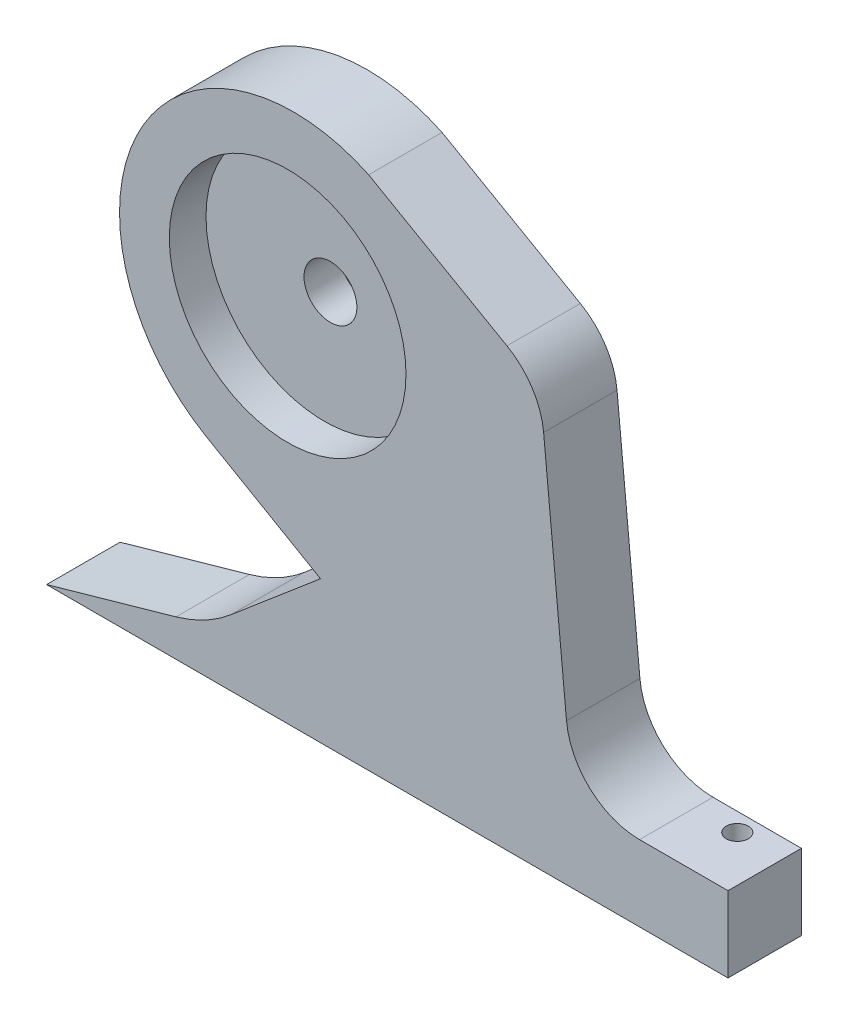
SolidWorks part; units mm, degrees
ref_plane "Front Plane" through (0, 0, 0) normal (0, 0, 1) x (1, 0, 0)
ref_plane "Top Plane" through (0, 0, 0) normal (0, 1, 0) x (1, 0, 0)
ref_plane "Right Plane" through (0, 0, 0) normal (1, 0, 0) x (0, 0, -1)
sketch "Sketch1" plane through (0, 0, 0) normal (0, 0, 1) x (1, 0, 0)
  line L0 (21.2946, 15.4992) -> (22.7802, 0.0334)
  line L2 (-2.5397, 33.9855) -> (16.2995, 23.2268)
  line L3 (22.7802, 0.0334) -> (24.4112, -16.9452)
  line L4 (34.3653, -25.989) -> (46.4112, -25.989)
  line L5 (-24.6077, -7.9899) -> (-9.0967, -16.9452)
  line L7 (46.4112, -25.989) -> (46.4112, -36.2909)
  line L8 (46.4112, -36.2909) -> (24.4112, -36.2909)
  line L9 (24.4112, -36.2909) -> (-46.4112, -36.2909)
  line L10 (-9.0967, -16.9452) -> (-21.306, -27.2953)
  line L11 (-28.7712, -31.2775) -> (-46.4112, -36.2909)
  arc A0 (-24.6077, -7.9899) -> (-2.5397, 33.9855) centre (-12.7427, 12.5609) cw
  arc A1 (24.4112, -16.9452) -> (34.3653, -25.989) centre (34.3653, -15.989) ccw
  arc A2 (21.2946, 15.4992) -> (16.2995, 23.2268) centre (11.3404, 14.543) ccw
  arc A3 (-21.306, -27.2953) -> (-28.7712, -31.2775) centre (-34.2388, -12.0394) cw
  dimension "D1" = 10
  dimension "D2" = 10
  dimension "D3" = 22
  dimension "D4" = 10.3019
  dimension "D5" = 12.0458
extrude "Boss-Extrude1" add sketch "Sketch1" along normal blind 10
sketch "Sketch4" plane through (0, 0, 10) normal (0, 0, 1) x (1, 0, 0)
  circle A0 centre (-13.5737, 12.9978) radius 16.12
  point P0 (0, 0)
  dimension "D1" = 32.24
  dimension "D2" = 23.7114
extrude "Cut-Extrude1" cut sketch "Sketch4" against normal blind 5 contours A0
sketch "Sketch5" plane through (0, -25.989, 0) normal (0, 1, 0) x (1, 0, 0)
  line L0 (46.4112, -10) -> (34.3653, -10) construction
  circle A0 centre (40.1734, -2.5) radius 1.5
  point P2 (0, 0)
  point P5 (0, 0)
  point P6 (40.3882, -10)
  dimension "D1" = 3
  dimension "D2" = 7.5
extrude "Cut-Extrude2" cut sketch "Sketch5" against normal up to surface (10.3019 mm away) up to face at (0, -36.2909, 5)
sketch "Sketch6" plane through (0, 0, 0) normal (0, 0, -1) x (-1, 0, 0)
  circle A2 centre (12.7427, 12.5609) radius 3.6
  dimension "D1" = 7.2
extrude "Cut-Extrude3" cut sketch "Sketch6" against normal up to surface (5 mm away) up to face at (2.5463, 12.9978, 5)
